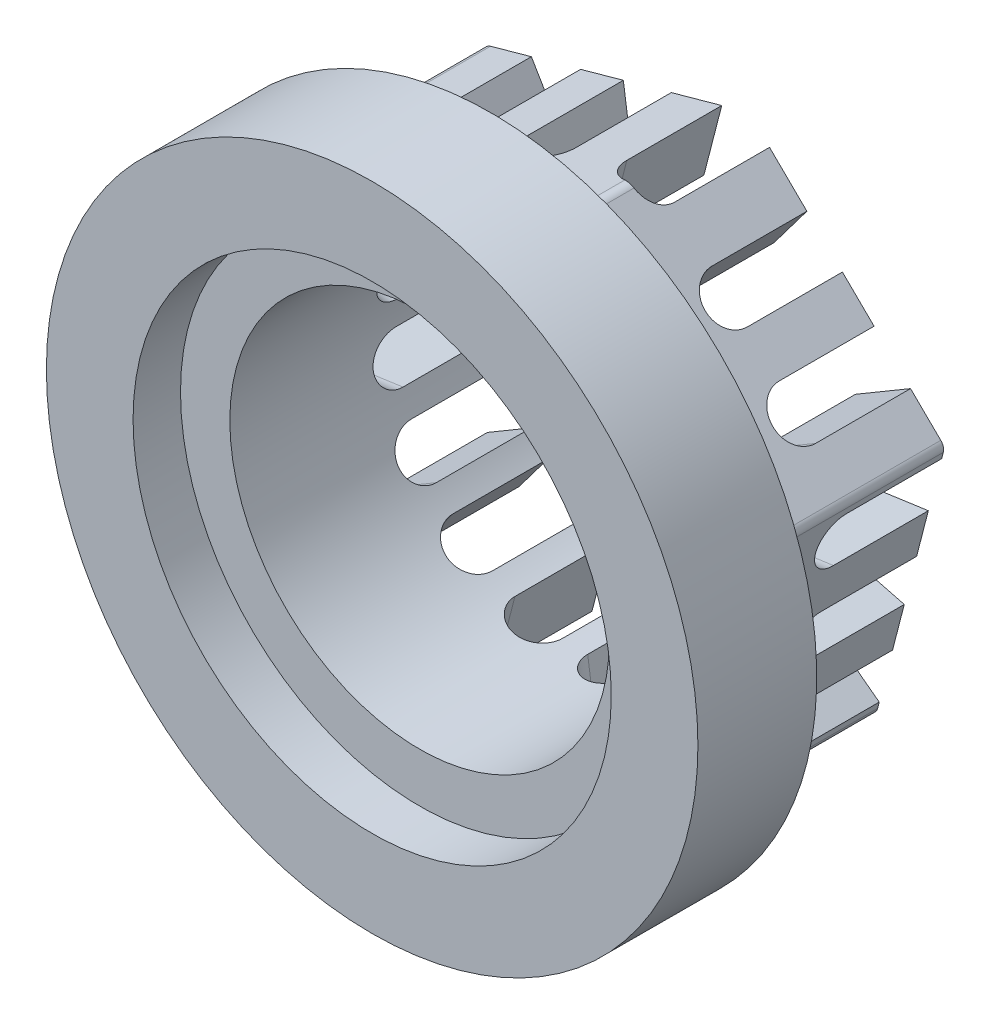
SolidWorks part; units mm, degrees
material "AISI Type 316L stainless steel"
ref_plane "Front Plane" through (0, 0, 0) normal (0, 0, 1) x (1, 0, 0)
ref_plane "Top Plane" through (0, 0, 0) normal (0, 1, 0) x (1, 0, 0)
ref_plane "Right Plane" through (0, 0, 0) normal (1, 0, 0) x (0, 0, -1)
sketch "Sketch1" plane through (0, 0, 0) normal (0, 0, 1) x (1, 0, 0)
  circle A0 centre (0, 0) radius 21.7995
  dimension "D1" = 43.5991
extrude "Boss-Extrude1" add sketch "Sketch1" along normal blind 20.6502
sketch "Sketch2" plane through (0, 0, 20.6502) normal (0, 0, 1) x (1, 0, 0)
  circle A0 centre (0, 0) radius 12.7
  dimension "D1" = 25.4
extrude "Cut-Extrude1" cut sketch "Sketch2" against normal blind 20.6502
sketch "Sketch3" plane through (0, 0, 20.6502) normal (0, 0, 1) x (1, 0, 0)
  circle A0 centre (0, 0) radius 16
  dimension "D1" = 32
extrude "Cut-Extrude2" cut sketch "Sketch3" against normal blind 3.175
sketch "Sketch4" plane through (0, 0, 0) normal (0, 0, -1) x (-1, 0, 0)
  line L1 (17.6618, -4.9073) -> (13.0808, 12.8419)
  line L2 (13.0808, 12.8419) -> (-4.581, 17.7492)
  line L3 (-4.581, 17.7492) -> (-17.6618, 4.9073)
  line L4 (-17.6618, 4.9073) -> (-13.0808, -12.8419)
  line L5 (-13.0808, -12.8419) -> (4.581, -17.7492)
  line L6 (4.581, -17.7492) -> (17.6618, -4.9073)
  circle A1 centre (0, 0) radius 15.875 construction
  dimension "D1" = 31.75
extrude "Cut-Extrude3" cut sketch "Sketch4" against normal blind 12.7 flip side to cut
sketch "Sketch5" plane through (-15.3713, 3.9673, 0) normal (-0.9683, 0.2499, 0) x (0, 0, 1)
  line L0 (0, 0) -> (12.7, 0) construction
  line L1 (12.7, -9.1654) -> (12.7, 9.1654) construction
  line L2 (6.35, 1.651) -> (0, 1.651)
  line L3 (0, -9.1654) -> (0, 9.1654) construction
  line L4 (0, 1.651) -> (0, -1.651)
  line L5 (0, -1.651) -> (6.35, -1.651)
  arc A1 (6.35, 1.651) -> (6.35, -1.651) centre (6.35, 0) cw
  point P6 (3.175, -1.651)
  dimension "D1" = 3.302
extrude "Cut-Extrude4" cut sketch "Sketch5" against normal blind 9.8552 and the other way blind 9.8552
pattern_circular "CirPattern1" count 16 over 360 about axis through (0, 0, 17.4752) along (0, 0, 1) of "Cut-Extrude4" reverse direction yes
fillet "Fillet1" radius 0.635 6 edges at (-17.6618, -4.9073, 6.35) (-13.0808, 12.8419, 6.35) (4.581, 17.7492, 10.3505) (17.6618, 4.9073, 6.35) (13.0808, -12.8419, 6.35) (-4.581, -17.7492, 10.3505)
ref_axis "Axis1" through (0, 0, 17.4752) along (0, 0, 1)
